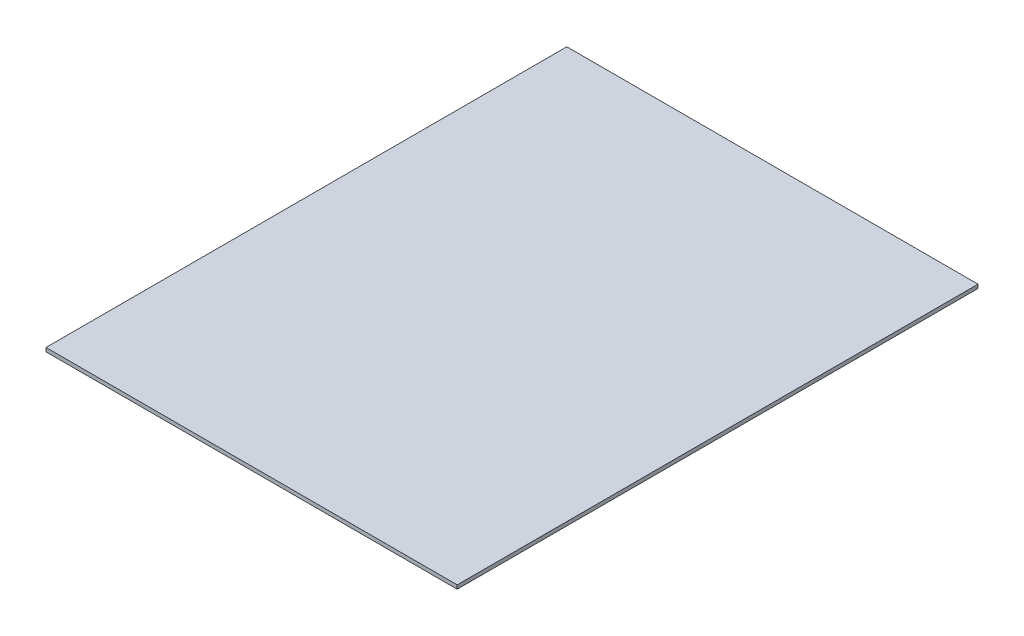
SolidWorks part; units mm, degrees
ref_plane "Front Plane" through (0, 0, 0) normal (0, 0, 1) x (1, 0, 0)
ref_plane "Top Plane" through (0, 0, 0) normal (0, 1, 0) x (1, 0, 0)
ref_plane "Right Plane" through (0, 0, 0) normal (1, 0, 0) x (0, 0, -1)
sketch "Sketch1" plane through (0, 0, 0) normal (0, 1, 0) x (1, 0, 0)
  line L1 (-163, 206.45) -> (163, 206.45)
  line L2 (-163, 206.45) -> (-163, -206.45)
  line L3 (-163, -206.45) -> (163, -206.45)
  line L4 (163, 206.45) -> (163, -206.45)
  line L5 (-163, 206.45) -> (163, -206.45) construction
  line L6 (-163, -206.45) -> (163, 206.45) construction
  point P0 (0, 0)
  dimension "D1" = 326
  dimension "D2" = 412.9
extrude "Boss-Extrude1" add sketch "Sketch1" along normal blind 3
